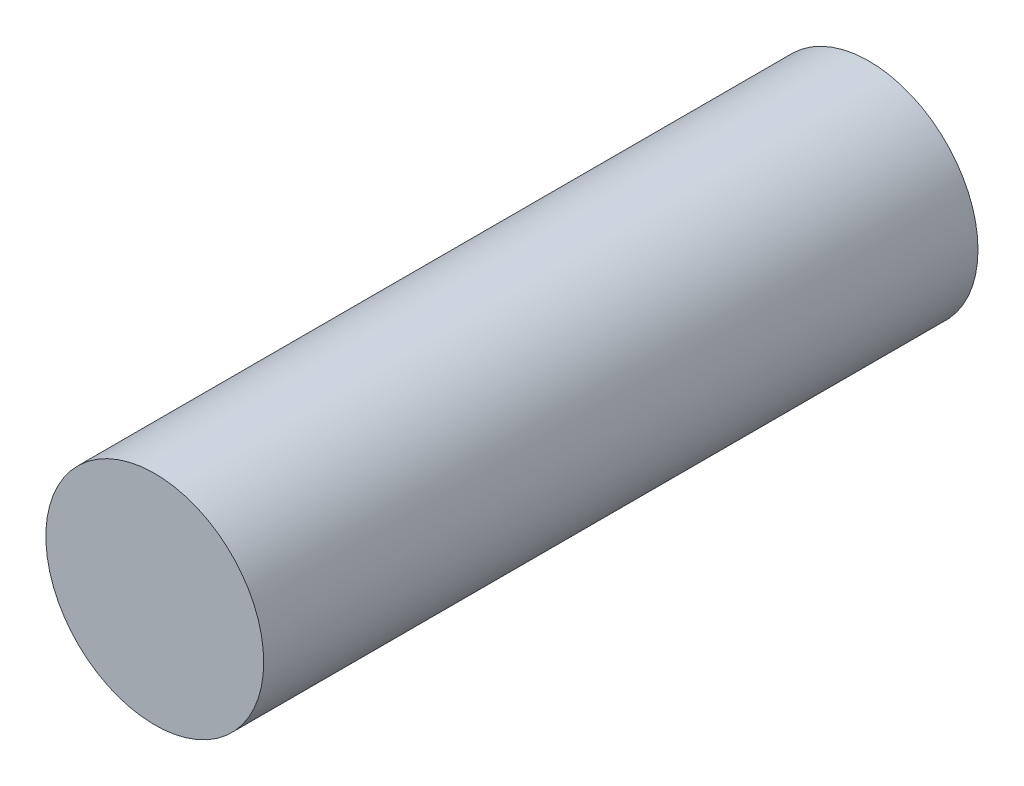
SolidWorks part; units mm, degrees
ref_plane "Front Plane" through (0, 0, 0) normal (0, 0, 1) x (1, 0, 0)
ref_plane "Top Plane" through (0, 0, 0) normal (0, 1, 0) x (1, 0, 0)
ref_plane "Right Plane" through (0, 0, 0) normal (1, 0, 0) x (0, 0, -1)
sketch "Sketch1" plane through (0, 0, 0) normal (0, 0, 1) x (1, 0, 0)
  circle A0 centre (0, 0) radius 3.05
  point P3 (0, 0)
  dimension "D1" = 6.1
extrude "Boss-Extrude1" add sketch "Sketch1" along normal blind 3 and the other way blind 17 contours A0
